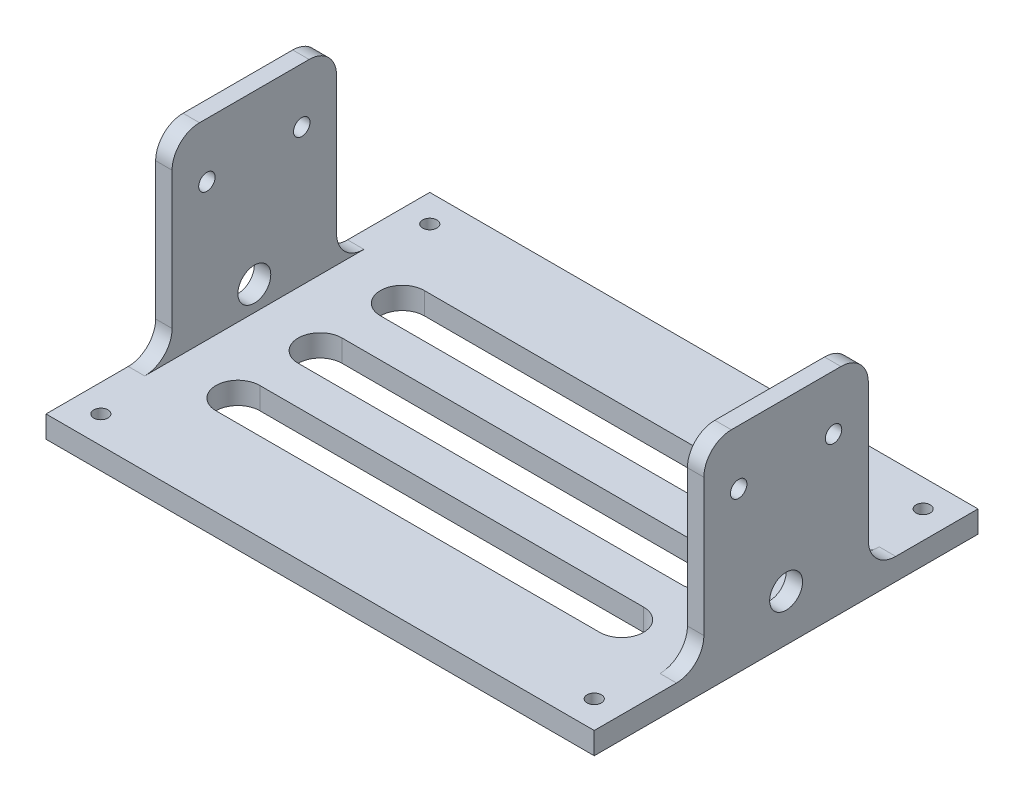
SolidWorks part; units mm, degrees
material "ABS"
ref_plane "Front Plane" through (0, 0, 0) normal (0, 0, 1) x (1, 0, 0)
ref_plane "Top Plane" through (0, 0, 0) normal (0, 1, 0) x (1, 0, 0)
ref_plane "Right Plane" through (0, 0, 0) normal (1, 0, 0) x (0, 0, -1)
sketch "Sketch1" plane through (0, 0, 0) normal (0, 1, 0) x (1, 0, 0)
  line L0 (0, 50) -> (3, 50)
  line L1 (0, 0) -> (100, 0)
  line L2 (0, 0) -> (0, 70)
  line L3 (0, 70) -> (100, 70)
  line L4 (100, 0) -> (100, 70)
  line L5 (3, 50) -> (3, 20)
  line L6 (3, 20) -> (0, 20)
  line L7 (50, 70) -> (50, 0) construction
  line L26 (0, 35) -> (100, 35) construction
  line L27 (15, 35) -> (85, 35) construction
  line L28 (15, 39) -> (85, 39)
  line L29 (15, 31) -> (85, 31)
  line L30 (15, 50) -> (85, 50) construction
  line L31 (15, 54) -> (85, 54)
  line L32 (15, 46) -> (85, 46)
  line L33 (15, 20) -> (85, 20) construction
  line L36 (15, 24) -> (85, 24)
  line L37 (15, 16) -> (85, 16)
  circle A0 centre (5, 65) radius 1.3
  circle A1 centre (5, 5) radius 1.3
  arc A4 (15, 39) -> (15, 31) centre (15, 35) ccw
  arc A5 (85, 31) -> (85, 39) centre (85, 35) ccw
  arc A6 (15, 54) -> (15, 46) centre (15, 50) ccw
  arc A7 (85, 46) -> (85, 54) centre (85, 50) ccw
  arc A10 (15, 24) -> (15, 16) centre (15, 20) ccw
  arc A11 (85, 16) -> (85, 24) centre (85, 20) ccw
  circle A12 centre (95, 65) radius 1.3
  circle A14 centre (95, 5) radius 1.3
  point P10 (50, 35)
  point P23 (50, 50)
  point P33 (50, 20)
  point P40 (89, 50)
  dimension "D1" = 2.6
  dimension "D2" = 2.6
  dimension "D3" = 4
  dimension "D4" = 70
  dimension "D5" = 5
  dimension "D6" = 5
  dimension "D7" = 5
  dimension "D8" = 5
  dimension "D10" = 7
  dimension "D11" = 70
  dimension "D14" = 4
  dimension "D16" = 4
  dimension "D22" = 4
  dimension "D9" = 70
  dimension "D12" = 15
  dimension "D13" = 4
  dimension "D15" = 70
  dimension "D17" = 100
  dimension "D18" = 5
  dimension "D19" = 5
  dimension "D20" = 5
  dimension "D21" = 5
  dimension "D25" = 20
  dimension "D26" = 3
  dimension "D27" = 20
extrude "Boss-Extrude10" add sketch "Sketch1" along normal blind 4 contours L1 L4 L3 L2 L0 L5 L6 A14 A12 A11 L37 A10 L36 A7 L32 A6 L31 A5 L29 A4 L28 A1 A0 region at (1.2207, 0, -60)
extrude "Boss-Extrude11" add sketch "Sketch1<22>" along normal blind 39 contours L6 L5 L0 L2 region at (1.5, 0, -35)
sketch "Sketch1<22>" plane through (0, 0, 0) normal (0, 1, 0) x (1, 0, 0) same geometry as "Sketch1"
fillet "Fillet4" radius 5 4 edges at (1.5, 4, -50) (1.5, 39, -50) (1.5, 4, -20) (1.5, 39, -20)
sketch "Sketch4" plane through (3, 0, 0) normal (1, 0, 0) x (0, 0, -1)
  line L0 (50, 34) -> (50, 9) construction
  line L1 (20, 34) -> (20, 9) construction
  line L2 (0, 0) -> (70, 0) construction
  line L3 (45, 39) -> (25, 39) construction
  circle A0 centre (26.35, 29) radius 1.5
  circle A1 centre (43.65, 29) radius 1.5
  circle A2 centre (35, 8.5) radius 3
  dimension "D4" = 3
  dimension "D5" = 3
  dimension "D9" = 6
  dimension "D1" = 15
  dimension "D2" = 6.35
  dimension "D3" = 6.35
  dimension "D6" = 8.5
  dimension "D7" = 10
  dimension "D8" = 10
  dimension "D10" = 17.3
extrude "Cut-Extrude19" cut sketch "Sketch4" against normal through all
ref_plane "Plane8" through (50, 0, 0) normal (1, 0, 0) x (0, 0, -1)
mirror "Mirror7" about plane through (50, 0, 0) normal (1, 0, 0) of bodies 114
